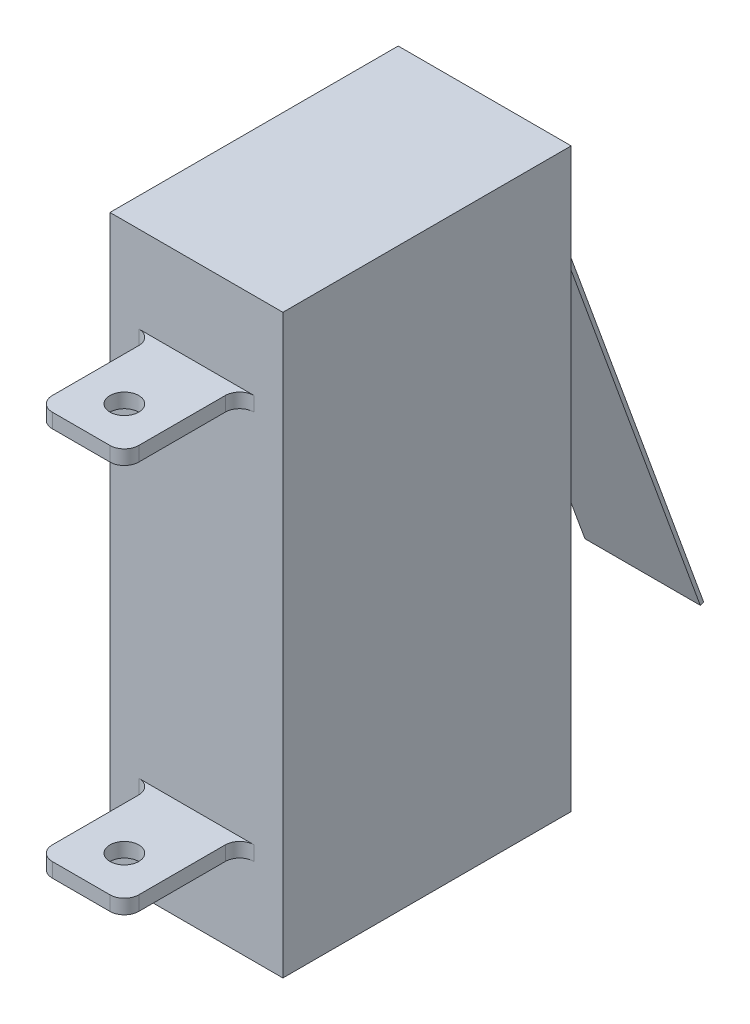
SolidWorks part; units mm, degrees
ref_plane "Front Plane" through (0, 0, 0) normal (0, 0, 1) x (1, 0, 0)
ref_plane "Top Plane" through (0, 0, 0) normal (0, 1, 0) x (1, 0, 0)
ref_plane "Right Plane" through (0, 0, 0) normal (1, 0, 0) x (0, 0, -1)
sketch "Sketch1" plane through (0, 0, 0) normal (1, 0, 0) x (0, 0, -1)
  line L1 (-5, 10) -> (5, 10)
  line L2 (-5, 10) -> (-5, -10)
  line L3 (-5, -10) -> (5, -10)
  line L4 (5, 10) -> (5, -10)
  line L5 (-5, 10) -> (5, -10) construction
  line L6 (-5, -10) -> (5, 10) construction
  point P0 (0, 0)
  dimension "D1" = 20
  dimension "D2" = 10
extrude "Boss-Extrude1" add sketch "Sketch1" along normal blind 6
sketch "Sketch2" plane through (0, 0, 5) normal (0, 0, 1) x (1, 0, 0)
  line L0 (0, 10) -> (0, -10) construction
  line L1 (1.5, 7) -> (4.5, 7)
  line L2 (1.5, 7) -> (1.5, 6.5)
  line L3 (1.5, 6.5) -> (4.5, 6.5)
  line L4 (4.5, 7) -> (4.5, 6.5)
  line L5 (1.5, -6.5) -> (4.5, -6.5)
  line L6 (1.5, -6.5) -> (1.5, -7)
  line L7 (1.5, -7) -> (4.5, -7)
  line L8 (4.5, -6.5) -> (4.5, -7)
  line L9 (6, 10) -> (6, -10) construction
  line L10 (6, 10) -> (0, 10) construction
  line L11 (6, -10) -> (0, -10) construction
  dimension "D1" = 1.5
  dimension "D2" = 1.5
  dimension "D3" = 3
  dimension "D4" = 0.5
  dimension "D5" = 3
  dimension "D6" = 0.5
extrude "Boss-Extrude2" add sketch "Sketch2" along normal blind 4
fillet "Fillet1" radius 0.5 8 edges at (4.5, -6.75, 5) (1.5, -6.75, 5) (1.5, -6.75, 9) (4.5, -6.75, 9) (1.5, 6.75, 5) (4.5, 6.75, 5) (1.5, 6.75, 9) (4.5, 6.75, 9)
sketch "Sketch3" plane through (0, 7, 0) normal (0, 1, 0) x (1, 0, 0)
  line L0 (4, -9) -> (2, -9) construction
  circle A0 centre (3, -7.5) radius 0.5
  point P4 (0, 0)
  point P5 (3, -9)
  dimension "D1" = 1
  dimension "D2" = 1.5
extrude "Cut-Extrude1" cut sketch "Sketch3" against normal through all both and the other way through all
ref_plane "Plane1" through (3, 0, 0) normal (1, 0, 0) x (0, 0, -1)
sketch "Sketch4" plane through (3, 0, 0) normal (1, 0, 0) x (0, 0, -1)
  line L0 (5, 7) -> (5.5, 7)
  line L1 (5, -10) -> (5, 10) construction
  line L2 (5.5, 7) -> (10.5956, -7)
  line L3 (5, 7) -> (4.5, 7)
  line L4 (5, 10) -> (-5, 10) construction
  line L5 (-5, -10) -> (5, -10) construction
  line L6 (5, 6.875) -> (4.5, 6.875)
  line L7 (5, 6.875) -> (5.4125, 6.875)
  line L8 (5.4125, 6.875) -> (10.4781, -7.0428)
  line L9 (10.4781, -7.0428) -> (10.5956, -7)
  line L10 (4.5, 6.875) -> (4.5, 7)
  dimension "D1" = 3
  dimension "D2" = 0.5
  dimension "D3" = 0.5
  dimension "D4" = 3
  dimension "D5" = 110
  dimension "D6" = 0.125
extrude "Boss-Extrude3" add sketch "Sketch4" along normal mid plane 4
fillet "Fillet2" radius 0.5 2 edges at (3, 6.875, -5.4125) (3, 7, -5.5)
fillet "Fillet3" radius 0.125 4 edges at (1, 6.9375, -5) (5, 6.9375, -5) (3, 6.875, -5) (3, 7, -5)
